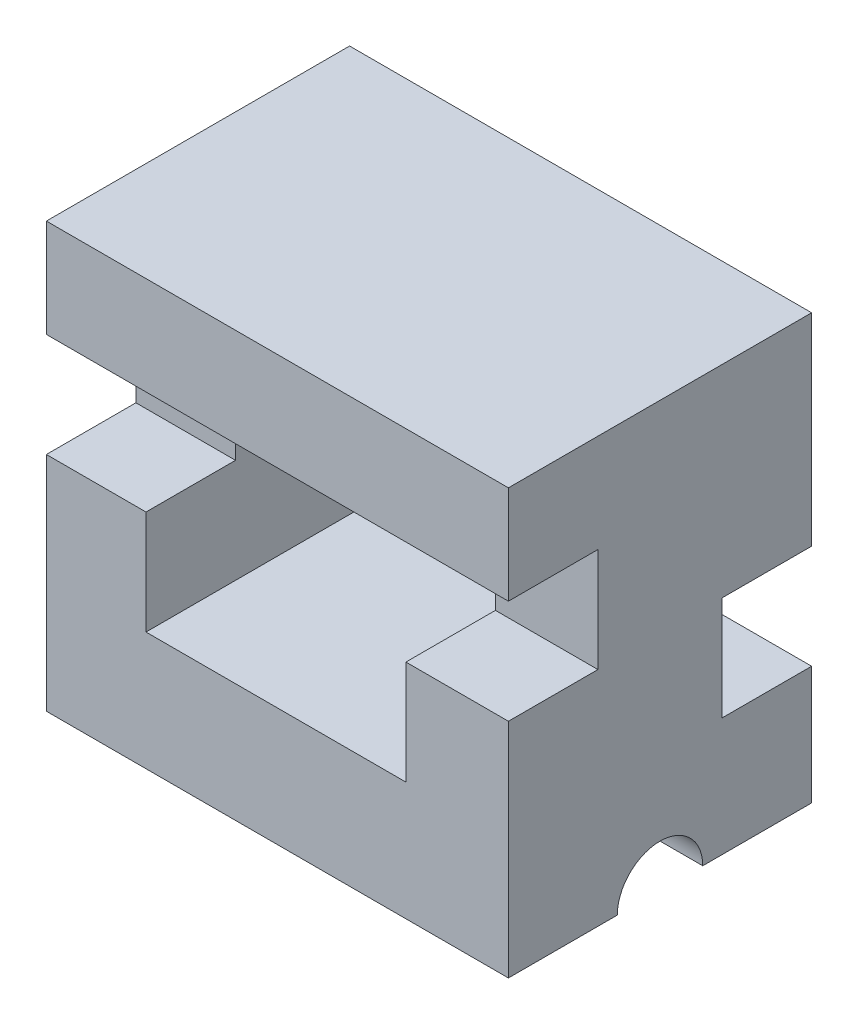
SolidWorks part; units mm, degrees
material "1.3# EPP"
ref_plane "Front Plane" through (0, 0, 0) normal (0, 0, 1) x (1, 0, 0)
ref_plane "Top Plane" through (0, 0, 0) normal (0, 1, 0) x (1, 0, 0)
ref_plane "Right Plane" through (0, 0, 0) normal (1, 0, 0) x (0, 0, -1)
sketch "Sketch2" plane through (0, 0, 0) normal (0, 1, 0) x (1, 0, 0)
  line L1 (0, 0) -> (40.64, 0)
  line L2 (0, 0) -> (0, 26.67)
  line L3 (0, 26.67) -> (40.64, 26.67)
  line L4 (40.64, 0) -> (40.64, 26.67)
  dimension "D1" = 26.67
  dimension "D2" = 40.64
extrude "Boss-Extrude1" add sketch "Sketch2" along normal blind 37.338
sketch "Sketch3" plane through (40.64, 0, 0) normal (1, 0, 0) x (0, 0, -1)
  line L0 (0, 0) -> (26.67, 0) construction
  circle A0 centre (13.335, 0) radius 3.7592
  dimension "D1" = 7.5184
extrude "Body Tube Cut" cut sketch "Sketch3" against normal through all
sketch "Sketch4" plane through (0, 0, 0) normal (0, 0, 1) x (1, 0, 0)
  line L0 (0, 0) -> (40.64, 0) construction
  line L1 (8.763, 28.702) -> (31.623, 28.702)
  line L2 (8.763, 28.702) -> (8.763, 10.414)
  line L3 (8.763, 10.414) -> (31.623, 10.414)
  line L4 (31.623, 28.702) -> (31.623, 10.414)
  line L5 (0, 37.338) -> (0, 0) construction
  dimension "D1" = 18.288
  dimension "D2" = 10.414
  dimension "D3" = 22.86
  dimension "D4" = 8.763
extrude "Servo Body Hole" cut sketch "Sketch4" against normal up to surface (26.67 mm away) up to face at (20.32, 18.669, -26.67)
sketch "Sketch5" plane through (40.64, 0, 0) normal (1, 0, 0) x (0, 0, -1)
  line L0 (26.67, 10.414) -> (0, 10.414) construction
  line L1 (26.67, 10.414) -> (0, 10.414)
  line L2 (26.67, 28.702) -> (0, 28.702) construction
  line L3 (26.67, 28.702) -> (0, 28.702)
  line L5 (0, 28.702) -> (7.874, 28.702)
  line L6 (0, 28.702) -> (0, 19.558)
  line L7 (0, 19.558) -> (7.874, 19.558)
  line L8 (7.874, 28.702) -> (7.874, 19.558)
  line L9 (26.67, 10.414) -> (18.796, 10.414)
  line L10 (26.67, 10.414) -> (26.67, 19.558)
  line L11 (26.67, 19.558) -> (18.796, 19.558)
  line L12 (18.796, 10.414) -> (18.796, 19.558)
  line M4 (26.67, 0) -> (26.67, 37.338)
  line M6 (0, 37.338) -> (0, 0)
  dimension "D1" = 9.144
  dimension "D2" = 7.874
  dimension "D3" = 7.874
  dimension "D4" = 9.144
extrude "Cut-Extrude3" cut sketch "Sketch5" against normal up to surface (40.64 mm away) contours L8 L3 L7 M6 | L12 L1 L11 M4 region at (40.64, 14.986, -22.733) region at (40.64, 24.13, -3.937) up to face at (0, 13.0725, -13.335)
